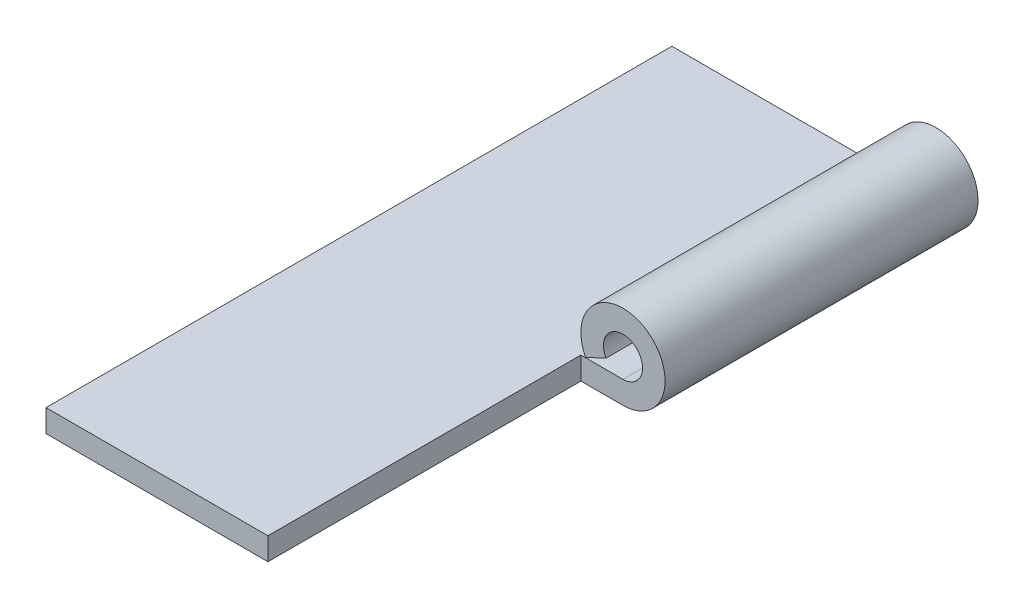
SolidWorks part; units mm, degrees
ref_plane "Front" through (0, 0, 0) normal (0, 0, 1) x (1, 0, 0)
ref_plane "Top" through (0, 0, 0) normal (0, 1, 0) x (1, 0, 0)
ref_plane "Right" through (0, 0, 0) normal (1, 0, 0) x (0, 0, -1)
sketch "Sketch1" plane through (0, 0, 0) normal (0, 0, 1) x (1, 0, 0)
  line L0 (-21.4312, 0) -> (0, 0)
  line L1 (-21.4312, 0) -> (-21.4312, 1.8288)
  line L2 (-21.4312, 1.8288) -> (0, 1.8288)
  line L3 (-21.4312, 0) -> (21.4312, 0) construction
  line L4 (-3.0382, 1.8542) -> (-1.3781, 2.6283)
  line L5 (-1.5875, 3.4163) -> (1.5875, 3.4163) construction
  line L6 (1.5875, 3.4163) -> (3.4163, 3.4163) construction
  line L7 (-1.5875, 3.4163) -> (-3.4163, 3.4163) construction
  circle A0 centre (0, 3.4163) radius 3.4163 construction
  circle A1 centre (0, 3.4163) radius 1.5875 construction
  arc A2 (0, 0) -> (-3.0382, 1.8542) centre (0, 3.4163) ccw
  arc A3 (0, 1.8288) -> (-1.3781, 2.6283) centre (0, 3.4163) ccw
  dimension "D1" = 25
  dimension "Pin Dia" = 3.175
  dimension "Thickness" = 1.8288
  dimension "Open Wd" = 42.8625
  dimension "D2" = 0.0254
extrude "Extrude1" add sketch "Sketch1" against normal blind 50.8
sketch "Sketch2" plane through (0, 0, 0) normal (0, 1, 0) x (1, 0, 0)
  line L0 (-3.4163, 50.8) -> (-3.4163, 0) construction
  line L1 (3.4163, 0) -> (-3.4163, 0)
  line L2 (3.4163, 0) -> (3.4163, 25.4)
  line L3 (3.4163, 25.4) -> (-3.4163, 25.4)
  line L4 (-3.4163, 0) -> (-3.4163, 25.4)
  dimension "D1" = 25.4
extrude "Cut-Extrude4" cut sketch "Sketch2" along normal through all
sketch "Sketch3" plane through (0, 0, 0) normal (0, 0, 1) x (1, 0, 0)
  line L0 (0, 0) -> (21.4312, 0)
  line L1 (21.4312, 0) -> (21.4312, 1.8288)
  line L2 (21.4312, 1.8288) -> (3.0251, 1.8288)
  line L3 (-21.4312, 1.8288) -> (0, 1.8288) construction
  arc A0 (0, 0) -> (3.0251, 1.8288) centre (0, 3.4163) cw
  arc A1 (0, 0) -> (-3.0382, 1.8542) centre (0, 3.4163) ccw construction
extrude "Extrude2" [suppressed] add sketch "Sketch3" against normal up to surface (50.8 mm away) separate body
sketch "Sketch4" [suppressed] plane through (0, 0, 0) normal (0, 1, 0) x (1, 0, 0)
  line L0 (3.4163, 50.8) -> (-3.4163, 50.8) construction
  line L1 (-3.4163, 25.4) -> (3.4163, 25.4)
  line L2 (-3.4163, 25.4) -> (-3.4163, 50.8)
  line L3 (-3.4163, 50.8) -> (3.4163, 50.8)
  line L4 (3.4163, 25.4) -> (3.4163, 50.8)
  line L5 (3.4163, 0) -> (3.4163, 50.8) construction
extrude "Cut-Extrude5" [suppressed] cut sketch "Sketch4" along normal through all
sketch "Sketch5" [suppressed] plane through (0, 0, -25.4) normal (0, 0, -1) x (-1, 0, 0)
  circle A0 centre (0, 3.4163) radius 1.5875
  arc A1 (1.3781, 2.6283) -> (0, 1.8288) centre (0, 3.4163) ccw construction
extrude "Extrude3" [suppressed] add sketch "Sketch5" along normal up to surface (25.4 mm away) separate body
ref_plane "Plane2" through (0, 3.4163, 0) normal (0, 1, 0) x (-1, 0, 0)
ref_axis "Axis1" [suppressed] through (0, 3.4163, -25.4) along (0, 0, 1)
sketch "Sketch9" [suppressed] plane through (0, 3.4163, 0) normal (0, 1, 0) x (-1, 0, 0)
  line L0 (0.3175, -50.8) -> (1.5875, -49.53)
  line L1 (-3.4163, -50.8) -> (3.4163, -50.8) construction
  line L3 (1.5875, -49.53) -> (1.5875, -50.8)
  line L4 (1.5875, -50.8) -> (0.3175, -50.8)
  line L5 (1.5875, -50.8) -> (1.5875, -25.4) construction
  dimension "D1" = 1.27
  dimension "D2" = 45
revolve "Cut-Revolve1" [suppressed] cut sketch "Sketch9" angle 360 about axis through (0, 3.4163, -25.4) along (0, 0, 1)
combine bodies "Combine1" [suppressed] operation type add bodies to combine 150 148
ref_plane "Plane1" through (0, 1.8288, 0) normal (0, 1, 0) x (-1, 0, 0)
sketch "Sketch6" [suppressed] plane through (0, 1.8288, 0) normal (0, 1, 0) x (-1, 0, 0)
  line L0 (21.4312, -50.8) -> (21.4312, 0) construction
  line L1 (-21.4312, -25.4) -> (21.4312, -25.4) construction
  line L2 (0, -50.8) -> (0, 0) construction
  line L3 (-21.4312, -50.8) -> (-21.4312, 0) construction
  line L4 (0, -50.8) -> (21.4312, -50.8) construction
  point P0 (13.4937, -41.275)
  point P1 (13.4937, -9.525)
  point P2 (-13.4937, -9.525)
  point P3 (-13.4937, -41.275)
  dimension "H2" = 9.525
  dimension "H1" = 7.9375
sketch "Sketch10" [suppressed] plane through (0, 0, 0) normal (0, 1, 0) x (1, 0, 0)
  circle A0 centre (13.4937, 9.525) radius 2.4574
  circle A1 centre (13.4937, 41.275) radius 2.4575
  circle A2 centre (-13.4937, 41.275) radius 2.4575
  circle A3 centre (-13.4937, 9.525) radius 2.4574
  dimension "Mounting Hole Dia." = 4.9149
extrude "Cut-Extrude7" [suppressed] cut sketch "Sketch10" against normal through all and the other way through all
equation "\"D1@Sketch2\" = \"D1@Extrude1\"/2"
